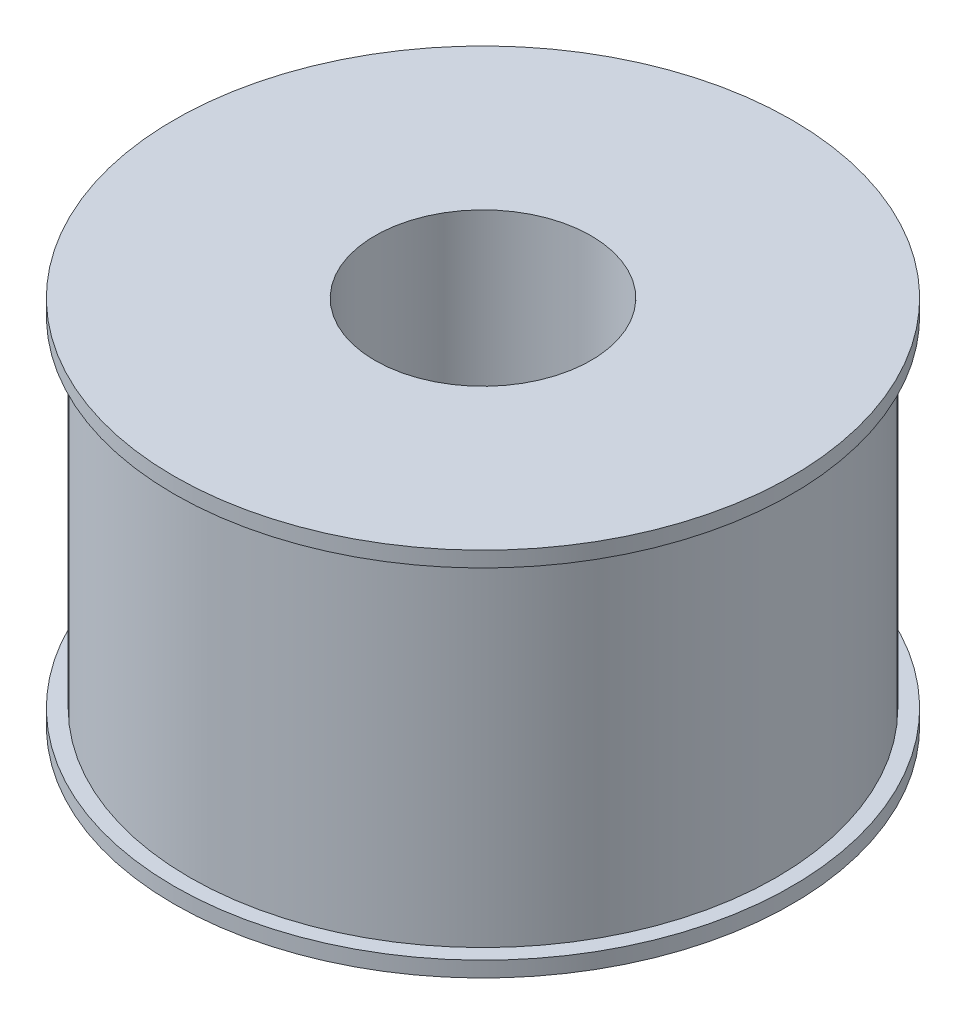
SolidWorks part; units mm, degrees
ref_plane "Front Plane" through (0, 0, 0) normal (0, 0, 1) x (1, 0, 0)
ref_plane "Top Plane" through (0, 0, 0) normal (0, 1, 0) x (1, 0, 0)
ref_plane "Right Plane" through (0, 0, 0) normal (1, 0, 0) x (0, 0, -1)
sketch "Sketch2" plane through (0, 0, 0) normal (0, 1, 0) x (1, 0, 0)
  circle A0 centre (0, 0) radius 10
  circle A1 centre (0, 0) radius 3.5
  dimension "D1" = 20
  dimension "D2" = 7
extrude "Boss-Extrude1" add sketch "Sketch2" along normal blind 12
sketch "Sketch3" plane through (0, 0, 0) normal (0, 0, 1) x (1, 0, 0)
  line L0 (-10, 12) -> (-10, 0) construction
  line L1 (-10.5, 0.5) -> (-9.5, 0.5)
  line L2 (-10.5, 0.5) -> (-10.5, 11.5)
  line L3 (-10.5, 11.5) -> (-9.5, 11.5)
  line L4 (-9.5, 0.5) -> (-9.5, 11.5)
  line L5 (-10.5, 0.5) -> (-9.5, 11.5) construction
  line L6 (-10.5, 11.5) -> (-9.5, 0.5) construction
  line L7 (10, 12) -> (-10, 12) construction
  line L8 (0, 12) -> (0, 0) construction
  point P0 (-10, 6)
  dimension "D1" = 0.5
  dimension "D2" = 1
revolve "Cut-Revolve1" cut sketch "Sketch3" angle 360 about L8
